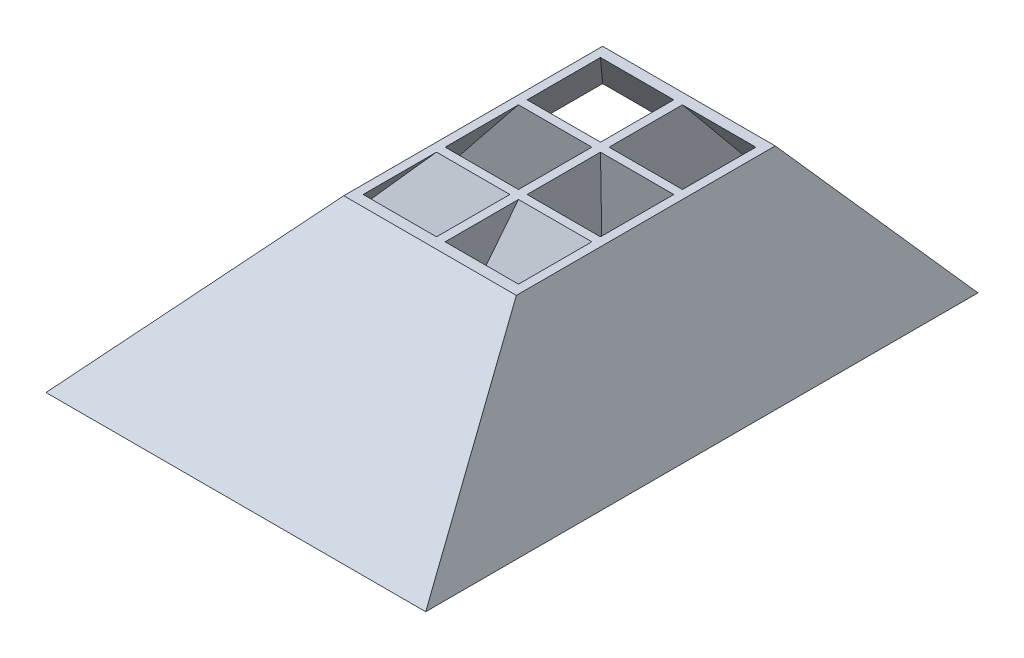
SolidWorks part; units mm, degrees
ref_plane "正面" through (0, 0, 0) normal (0, 0, 1) x (1, 0, 0)
ref_plane "平面" through (0, 0, 0) normal (0, 1, 0) x (1, 0, 0)
ref_plane "右側面" through (0, 0, 0) normal (1, 0, 0) x (0, 0, -1)
sketch "ｽｹｯﾁ1" plane through (0, 0, 0) normal (0, 0, 1) x (1, 0, 0)
  line L4 (0, 0) -> (44, 0)
  line L5 (44, 0) -> (37.5016, 20)
  line L6 (37.5016, 20) -> (17.5016, 20)
  line L7 (17.5016, 20) -> (0, 0)
  dimension "D1" = 44
  dimension "D2" = 20
  dimension "D3" = 72
  dimension "D4" = 20
extrude "ﾎﾞｽ - 押し出し1" add sketch "ｽｹｯﾁ1" along normal blind 64 contours L6 L7 L4 L5
ref_plane "平面3" through (17.5016, 0, 0) normal (-1, 0, 0) x (0, 0, 1)
sketch "ｽｹｯﾁ2" plane through (17.5016, 0, 0) normal (-1, 0, 0) x (0, 0, 1)
  line L0 (0, 0) -> (17, 20)
  line L1 (64, 20) -> (0, 20) construction
  line L2 (17, 20) -> (0, 20)
  line L3 (0, 20) -> (0, 0)
  line L4 (64, 0) -> (47, 20)
  line L5 (47, 20) -> (64, 20)
  line L6 (64, 20) -> (64, 0)
  dimension "D1" = 17
  dimension "D2" = 17
extrude "ｶｯﾄ - 押し出し1" cut sketch "ｽｹｯﾁ2" against normal through all both and the other way through all
sketch "ｽｹｯﾁ3" plane through (0, 0, 0) normal (0, -1, 0) x (1, 0, 0)
  line L0 (44, 64) -> (44, 0) construction
  line L1 (22.25, 63.25) -> (42.75, 63.25)
  line L2 (22.25, 63.25) -> (22.25, 42.75)
  line L3 (22.25, 42.75) -> (42.75, 42.75)
  line L4 (42.75, 63.25) -> (42.75, 42.75)
  line L5 (0, 64) -> (44, 64) construction
  line L6 (1.25, 63.25) -> (1.25, 42.75)
  line L7 (1.25, 63.25) -> (21.75, 63.25)
  line L8 (21.75, 63.25) -> (21.75, 42.75)
  line L9 (1.25, 42.75) -> (21.75, 42.75)
  line L10 (1.25, 42.25) -> (1.25, 21.75)
  line L11 (1.25, 21.75) -> (21.75, 21.75)
  line L12 (21.75, 42.25) -> (21.75, 21.75)
  line L13 (1.25, 42.25) -> (21.75, 42.25)
  line L14 (22.25, 42.25) -> (22.25, 21.75)
  line L15 (22.25, 42.25) -> (42.75, 42.25)
  line L16 (42.75, 42.25) -> (42.75, 21.75)
  line L17 (22.25, 21.75) -> (42.75, 21.75)
  line L18 (1.25, 21.25) -> (1.25, 0.75)
  line L19 (1.25, 0.75) -> (21.75, 0.75)
  line L20 (21.75, 21.25) -> (21.75, 0.75)
  line L21 (1.25, 21.25) -> (21.75, 21.25)
  line L22 (22.25, 21.25) -> (22.25, 0.75)
  line L23 (22.25, 21.25) -> (42.75, 21.25)
  line L24 (42.75, 21.25) -> (42.75, 0.75)
  line L25 (22.25, 0.75) -> (42.75, 0.75)
  dimension "D1" = 20.5
  dimension "D2" = 20.5
  dimension "D3" = 1.25
  dimension "D4" = 0.75
  dimension "D5" = 2
  dimension "D6" = 3
sketch "ｽｹｯﾁ4" plane through (0, 20, 0) normal (0, 1, 0) x (1, 0, 0)
  line L0 (37.5016, -17) -> (17.5016, -17) construction
  line L1 (28.0016, -18.25) -> (36.5016, -18.25)
  line L2 (28.0016, -18.25) -> (28.0016, -26.75)
  line L3 (28.0016, -26.75) -> (36.5016, -26.75)
  line L4 (36.5016, -18.25) -> (36.5016, -26.75)
  line L5 (37.5016, -47) -> (37.5016, -17) construction
  line L6 (18.5016, -18.25) -> (18.5016, -26.75)
  line L7 (18.5016, -18.25) -> (27.0016, -18.25)
  line L8 (27.0016, -18.25) -> (27.0016, -26.75)
  line L9 (18.5016, -26.75) -> (27.0016, -26.75)
  line L10 (28.0016, -27.75) -> (28.0016, -36.25)
  line L11 (28.0016, -27.75) -> (36.5016, -27.75)
  line L12 (36.5016, -27.75) -> (36.5016, -36.25)
  line L13 (28.0016, -36.25) -> (36.5016, -36.25)
  line L14 (18.5016, -27.75) -> (18.5016, -36.25)
  line L15 (18.5016, -36.25) -> (27.0016, -36.25)
  line L16 (27.0016, -27.75) -> (27.0016, -36.25)
  line L17 (18.5016, -27.75) -> (27.0016, -27.75)
  line L18 (28.0016, -37.25) -> (28.0016, -45.75)
  line L19 (28.0016, -37.25) -> (36.5016, -37.25)
  line L20 (36.5016, -37.25) -> (36.5016, -45.75)
  line L21 (28.0016, -45.75) -> (36.5016, -45.75)
  line L22 (18.5016, -37.25) -> (18.5016, -45.75)
  line L23 (18.5016, -45.75) -> (27.0016, -45.75)
  line L24 (27.0016, -37.25) -> (27.0016, -45.75)
  line L25 (18.5016, -37.25) -> (27.0016, -37.25)
  dimension "D1" = 8.5
  dimension "D2" = 8.5
  dimension "D3" = 1.25
  dimension "D4" = 1
  dimension "D5" = 2
  dimension "D6" = 3
loft "ｶｯﾄ - ﾛﾌﾄ1" cut section "ｽｹｯﾁ4" section "ｽｹｯﾁ3"
loft "ｶｯﾄ - ﾛﾌﾄ2" cut section "ｽｹｯﾁ4<3>" section "ｽｹｯﾁ3<3>"
sketch "ｽｹｯﾁ4<3>" plane through (0, 20, 0) normal (0, 1, 0) x (1, 0, 0) same geometry as "ｽｹｯﾁ4"
sketch "ｽｹｯﾁ3<3>" plane through (0, 0, 0) normal (0, -1, 0) x (1, 0, 0) same geometry as "ｽｹｯﾁ3"
loft "ｶｯﾄ - ﾛﾌﾄ3" cut section "ｽｹｯﾁ4<4>" section "ｽｹｯﾁ3<4>"
sketch "ｽｹｯﾁ4<4>" plane through (0, 20, 0) normal (0, 1, 0) x (1, 0, 0) same geometry as "ｽｹｯﾁ4"
sketch "ｽｹｯﾁ3<4>" plane through (0, 0, 0) normal (0, -1, 0) x (1, 0, 0) same geometry as "ｽｹｯﾁ3"
loft "ｶｯﾄ - ﾛﾌﾄ4" cut section "ｽｹｯﾁ4<5>" section "ｽｹｯﾁ3<5>"
sketch "ｽｹｯﾁ4<5>" plane through (0, 20, 0) normal (0, 1, 0) x (1, 0, 0) same geometry as "ｽｹｯﾁ4"
sketch "ｽｹｯﾁ3<5>" plane through (0, 0, 0) normal (0, -1, 0) x (1, 0, 0) same geometry as "ｽｹｯﾁ3"
loft "ｶｯﾄ - ﾛﾌﾄ5" cut section "ｽｹｯﾁ4<6>" section "ｽｹｯﾁ3<6>"
sketch "ｽｹｯﾁ4<6>" plane through (0, 20, 0) normal (0, 1, 0) x (1, 0, 0) same geometry as "ｽｹｯﾁ4"
sketch "ｽｹｯﾁ3<6>" plane through (0, 0, 0) normal (0, -1, 0) x (1, 0, 0) same geometry as "ｽｹｯﾁ3"
loft "ｶｯﾄ - ﾛﾌﾄ6" cut section "ｽｹｯﾁ4<7>" section "ｽｹｯﾁ3<7>"
sketch "ｽｹｯﾁ4<7>" plane through (0, 20, 0) normal (0, 1, 0) x (1, 0, 0) same geometry as "ｽｹｯﾁ4"
sketch "ｽｹｯﾁ3<7>" plane through (0, 0, 0) normal (0, -1, 0) x (1, 0, 0) same geometry as "ｽｹｯﾁ3"
